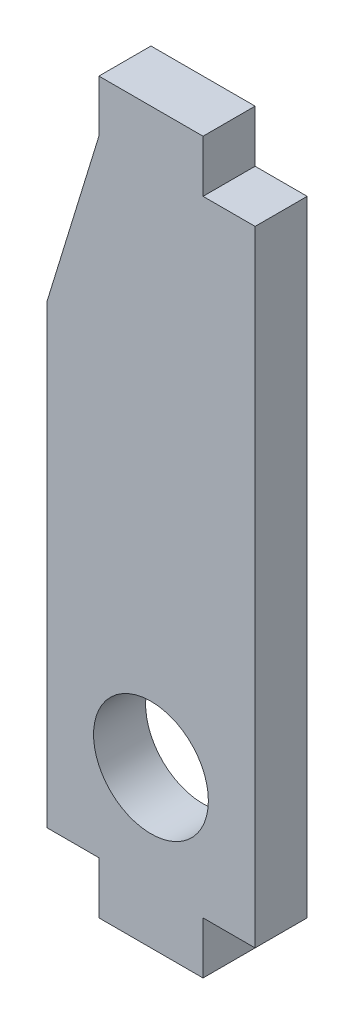
SolidWorks part; units mm, degrees
material "1060 Alloy"
ref_plane "Front Plane" through (0, 0, 0) normal (0, 0, 1) x (1, 0, 0)
ref_plane "Top Plane" through (0, 0, 0) normal (0, 1, 0) x (1, 0, 0)
ref_plane "Right Plane" through (0, 0, 0) normal (1, 0, 0) x (0, 0, -1)
sketch "Sketch1" plane through (0, 0, 0) normal (0, 0, 1) x (1, 0, 0)
  line L0 (55, 0) -> (-55, 0) construction
  line L1 (-12.7, -38.1) -> (12.7, -38.1)
  line L2 (-12.7, -38.1) -> (-12.7, 38.1)
  line L3 (-12.7, 38.1) -> (12.7, 38.1)
  line L4 (12.7, -38.1) -> (12.7, 38.1)
  line L5 (-12.7, -38.1) -> (12.7, 38.1) construction
  line L6 (-12.7, 38.1) -> (12.7, -38.1) construction
  line L7 (-12.7, 38.1) -> (12.7, 38.1)
  line L8 (-12.7, 38.1) -> (-12.7, 44.45)
  line L9 (-12.7, 44.45) -> (12.7, 44.45)
  line L10 (12.7, 38.1) -> (12.7, 44.45)
  line L11 (-12.7, -44.45) -> (12.7, -44.45)
  line L12 (12.7, -38.1) -> (12.7, -44.45)
  line L13 (-12.7, -38.1) -> (12.7, -38.1)
  line L14 (-12.7, -38.1) -> (-12.7, -44.45)
  line L15 (0, 44.45) -> (0, -44.45) construction
  line L16 (-6.35, -38.1) -> (6.35, -38.1)
  line L17 (-6.35, -38.1) -> (-6.35, -44.45)
  line L18 (-6.35, -44.45) -> (6.35, -44.45)
  line L19 (6.35, -38.1) -> (6.35, -44.45)
  line L21 (-6.35, 38.1) -> (6.35, 38.1)
  line L22 (-6.35, 38.1) -> (-6.35, 44.45)
  line L23 (-6.35, 44.45) -> (6.35, 44.45)
  line L24 (6.35, 38.1) -> (6.35, 44.45)
  point P0 (0, 0)
  point P10 (0, 44.45)
  point P11 (0, 38.1)
  point P18 (0, -38.1)
  point P19 (0, -44.45)
  point P30 (-6.35, 41.275)
  dimension "D1" = 25.4
  dimension "D2" = 76.2
  dimension "D3" = 25.4
  dimension "D4" = 6.35
  dimension "D5" = 12.7
  dimension "D6" = 12.7
extrude "Boss-Extrude1" add sketch "Sketch1" along normal blind 6.35 contours L1 L4 L3 L2 | L17 L16 L19 L18 | L22 L21 L24 L23 region at (0, 0, 0)
sketch "Sketch2" plane through (0, 0, 6.35) normal (0, 0, 1) x (1, 0, 0)
  line L0 (-6.35, 38.1) -> (-12.7, 17.4092)
  line L7 (-12.7, 38.1) -> (-6.35, 38.1) construction
  line L8 (-12.7, -38.1) -> (-6.35, -38.1) construction
  line L9 (-12.7, -38.1) -> (-12.7, 38.1) construction
  line L10 (-12.7, 17.4092) -> (-12.7, 38.1)
  line L11 (-12.7, 38.1) -> (-6.35, 38.1)
  circle A1 centre (0, -25.4) radius 7
  dimension "D2" = 12.7
  dimension "D1" = 14
extrude "Cut-Extrude1" cut sketch "Sketch2" against normal through all
